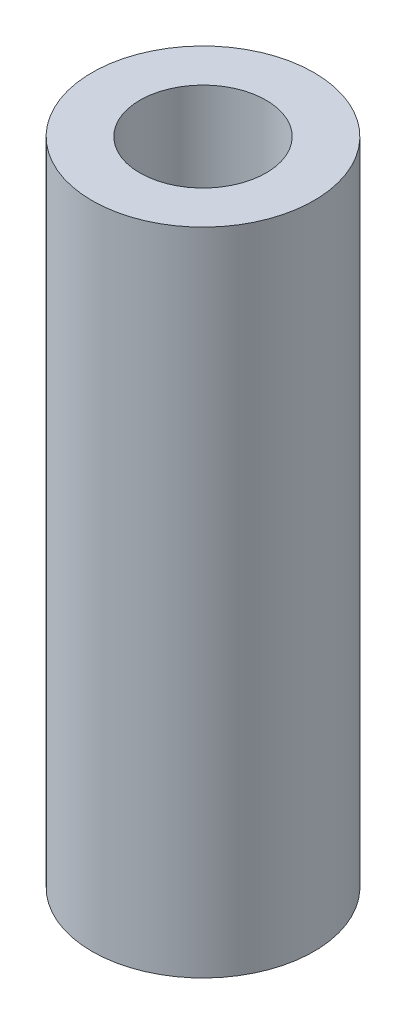
SolidWorks part; units mm, degrees
ref_plane "Front Plane" through (0, 0, 0) normal (0, 0, 1) x (1, 0, 0)
ref_plane "Top Plane" through (0, 0, 0) normal (0, 1, 0) x (1, 0, 0)
ref_plane "Right Plane" through (0, 0, 0) normal (1, 0, 0) x (0, 0, -1)
sketch "Sketch1" plane through (0, 0, 0) normal (0, 1, 0) x (1, 0, 0)
  circle A0 centre (0, 0) radius 10
  dimension "SLEEVE_OD" = 20
extrude "Boss-Extrude1" add sketch "Sketch1" along normal blind 58.6083
sketch "Sketch2" plane through (0, 0, 0) normal (0, 1, 0) x (1, 0, 0)
  circle A0 centre (0, 0) radius 5.6873
  dimension "BORE_D" = 11.3747
extrude "Cut-Extrude1" cut sketch "Sketch2" along normal through all
chamfer "Chamfer1" distance 1.6051 angle 60 rebuild error yes
